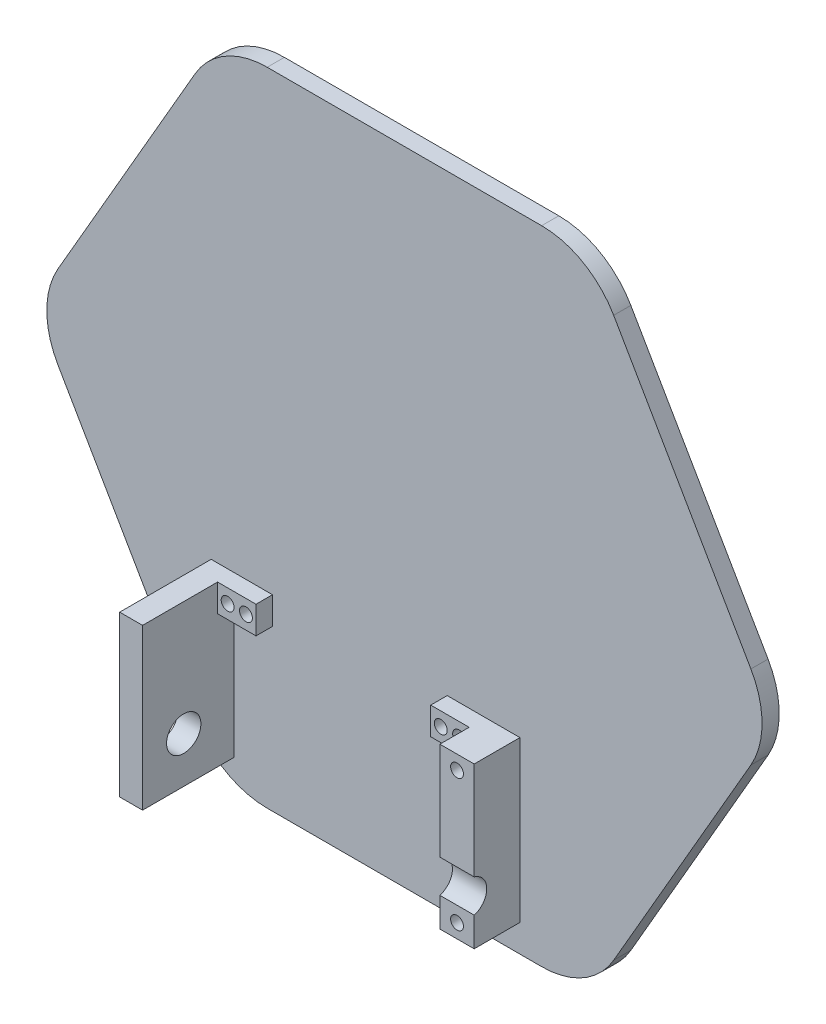
SolidWorks part; units mm, degrees
ref_plane "Front Plane" through (0, 0, 0) normal (0, 0, 1) x (1, 0, 0)
ref_plane "Top Plane" through (0, 0, 0) normal (0, 1, 0) x (1, 0, 0)
ref_plane "Right Plane" through (0, 0, 0) normal (1, 0, 0) x (0, 0, -1)
sketch "Sketch2" plane through (0, 0, 0) normal (0, 0, 1) x (1, 0, 0)
  line L1 (96.2019, 11.5481) -> (58.1019, 77.5392)
  line L2 (38.1, 89.0873) -> (-38.1, 89.0873)
  line L3 (-58.1019, 77.5392) -> (-96.2019, 11.5481)
  line L4 (-96.2019, -11.5481) -> (-58.1019, -77.5392)
  line L5 (-38.1, -89.0873) -> (38.1, -89.0873)
  line L6 (58.1019, -77.5392) -> (96.2019, -11.5481)
  circle A0 centre (0, 0) radius 89.0873 construction
  arc A1 (58.1019, 77.5392) -> (38.1, 89.0873) centre (38.1, 65.9911) ccw
  arc A2 (96.2019, 11.5481) -> (96.2019, -11.5481) centre (76.2, 0) cw
  arc A3 (38.1, -89.0873) -> (58.1019, -77.5392) centre (38.1, -65.9911) ccw
  arc A4 (-58.1019, -77.5392) -> (-38.1, -89.0873) centre (-38.1, -65.9911) ccw
  arc A5 (-96.2019, 11.5481) -> (-96.2019, -11.5481) centre (-76.2, 0) ccw
  arc A6 (-38.1, 89.0873) -> (-58.1019, 77.5392) centre (-38.1, 65.9911) ccw
  dimension "D1" = 76.2
extrude "Boss-Extrude1" add sketch "Sketch2" along normal blind 4.7625
sketch "Sketch4" plane through (0, 0, 4.7625) normal (0, 0, 1) x (1, 0, 0)
  line L0 (-38.1, -89.0873) -> (38.1, -89.0873) construction
  line L1 (-53.6569, -81.4673) -> (-47.3069, -81.4673)
  line L2 (-53.6569, -81.4673) -> (-53.6569, -37.0173)
  line L3 (-53.6569, -37.0173) -> (-47.3069, -37.0173)
  line L4 (-47.3069, -81.4673) -> (-47.3069, -37.0173)
  point P17 (0, 0)
  dimension "D1" = 6.35
  dimension "D2" = 44.45
  dimension "D3" = 7.62
  dimension "D4" = 4.445
extrude "Boss-Extrude3" add sketch "Sketch4" along normal blind 25.4
sketch "Sketch5" plane through (0, 0, 4.7625) normal (0, 0, 1) x (1, 0, 0)
  line L0 (-47.3069, -81.4673) -> (-47.3069, -37.0173) construction
  line L1 (22.5431, -81.4673) -> (32.0681, -81.4673)
  line L2 (22.5431, -81.4673) -> (22.5431, -37.0173)
  line L3 (22.5431, -37.0173) -> (32.0681, -37.0173)
  line L4 (32.0681, -81.4673) -> (32.0681, -37.0173)
  line L6 (-53.6569, -81.4673) -> (-47.3069, -81.4673) construction
  point P19 (0, 0)
  dimension "D1" = 9.525
  dimension "D2" = 69.85
extrude "Boss-Extrude6" add sketch "Sketch5" along normal blind 12.7
sketch "Sketch6" plane through (0, 0, 4.7625) normal (0, 0, 1) x (1, 0, 0)
  line L0 (11.8751, -37.0173) -> (22.5431, -37.0173)
  line L1 (-47.3069, -37.0173) -> (-36.6389, -37.0173)
  line L2 (-47.3069, -37.0173) -> (-47.3069, -44.6373)
  line L3 (-47.3069, -44.6373) -> (-36.6389, -44.6373)
  line L4 (-36.6389, -37.0173) -> (-36.6389, -44.6373)
  line L5 (11.8751, -37.0173) -> (11.8751, -44.6373)
  line L6 (11.8751, -44.6373) -> (22.5431, -44.6373)
  line L7 (22.5431, -37.0173) -> (22.5431, -44.6373)
  line L8 (22.5431, -37.0173) -> (22.5431, -81.4673) construction
  line L9 (32.0681, -37.0173) -> (22.5431, -37.0173) construction
  line L11 (-47.3069, -81.4673) -> (-47.3069, -37.0173) construction
  point P16 (0, 0)
  dimension "D1" = 7.62
  dimension "D2" = 10.668
  dimension "D3" = 7.62
  dimension "D4" = 10.668
extrude "Boss-Extrude5" add sketch "Sketch6" along normal blind 4.572
sketch "Sketch7" plane through (0, 0, 9.3345) normal (0, 0, 1) x (1, 0, 0)
  line L0 (-47.3069, -44.6373) -> (-36.6389, -44.6373) construction
  line L1 (-36.6389, -44.6373) -> (-36.6389, -37.0173) construction
  line L2 (11.8751, -44.6373) -> (22.5431, -44.6373) construction
  line L3 (11.8751, -37.0173) -> (11.8751, -44.6373) construction
  circle A0 centre (-44.5129, -40.8273) radius 1.7907
  circle A1 centre (-39.4329, -40.8273) radius 1.7907
  circle A2 centre (14.6691, -40.8273) radius 1.7907
  circle A3 centre (19.7491, -40.8273) radius 1.7907
  dimension "D1" = 3.5814
  dimension "D2" = 3.81
  dimension "D8" = 3.5814
  dimension "D9" = 3.5814
  dimension "D10" = 3.5814
  dimension "D3" = 5.08
  dimension "D4" = 2.794
  dimension "D5" = 3.81
  dimension "D6" = 2.794
  dimension "D7" = 5.08
extrude "Cut-Extrude1" cut sketch "Sketch7" against normal blind 6.731
sketch "Sketch9" plane through (-53.6569, 0, 0) normal (-1, 0, 0) x (0, 0, 1)
  line L0 (4.7625, -37.0173) -> (4.7625, -81.4673) construction
  line L1 (30.1625, -81.4673) -> (4.7625, -81.4673) construction
  circle A0 centre (7.5311, -68.7673) radius 2.286
  dimension "D1" = 4.572
  dimension "D2" = 2.7686
  dimension "D3" = 12.7
sketch "Sketch10" plane through (-53.6569, 0, 0) normal (-1, 0, 0) x (0, 0, 1)
  line L0 (30.1625, -81.4673) -> (4.7625, -81.4673) construction
  circle A0 centre (18.7325, -68.7673) radius 4.7625
  dimension "D1" = 9.525
  dimension "D2" = 11.2014
  dimension "D3" = 12.7
extrude "Cut-Extrude3" cut sketch "Sketch9" against normal blind 2.54
extrude "Cut-Extrude4" cut sketch "Sketch10" against normal up to surface (6.35 mm away) up to face at (-47.3069, -54.374, 14.7532)
sketch3d "3DSketch1"
  line L0 (0, 0, 0) -> (0, 0, 50000) construction
sketch "Sketch11" plane through (22.5431, 0, 0) normal (-1, 0, 0) x (0, 0, 1)
  circle A0 centre (18.7325, -68.7673) radius 4.7625 construction
  circle A1 centre (18.7325, -68.7673) radius 4.7625 construction
  circle A2 centre (18.7325, -68.7673) radius 4.7625
  dimension "D1" = 9.525
extrude "Cut-Extrude5" cut sketch "Sketch11" against normal through all
sketch "Sketch12" plane through (0, 0, 17.4625) normal (0, 0, 1) x (1, 0, 0)
  line L0 (32.0681, -64.1773) -> (32.0681, -37.0173) construction
  line L2 (22.5431, -81.4673) -> (32.0681, -81.4673) construction
  line L3 (32.0681, -37.0173) -> (22.5431, -37.0173) construction
  circle A0 centre (27.3056, -40.9162) radius 1.778
  circle A1 centre (27.3056, -77.5684) radius 1.778
  dimension "D1" = 3.556
  dimension "D4" = 3.556
  dimension "D2" = 4.7625
  dimension "D3" = 3.8989
  dimension "D5" = 3.8989
extrude "Cut-Extrude6" cut sketch "Sketch12" against normal blind 6.731
